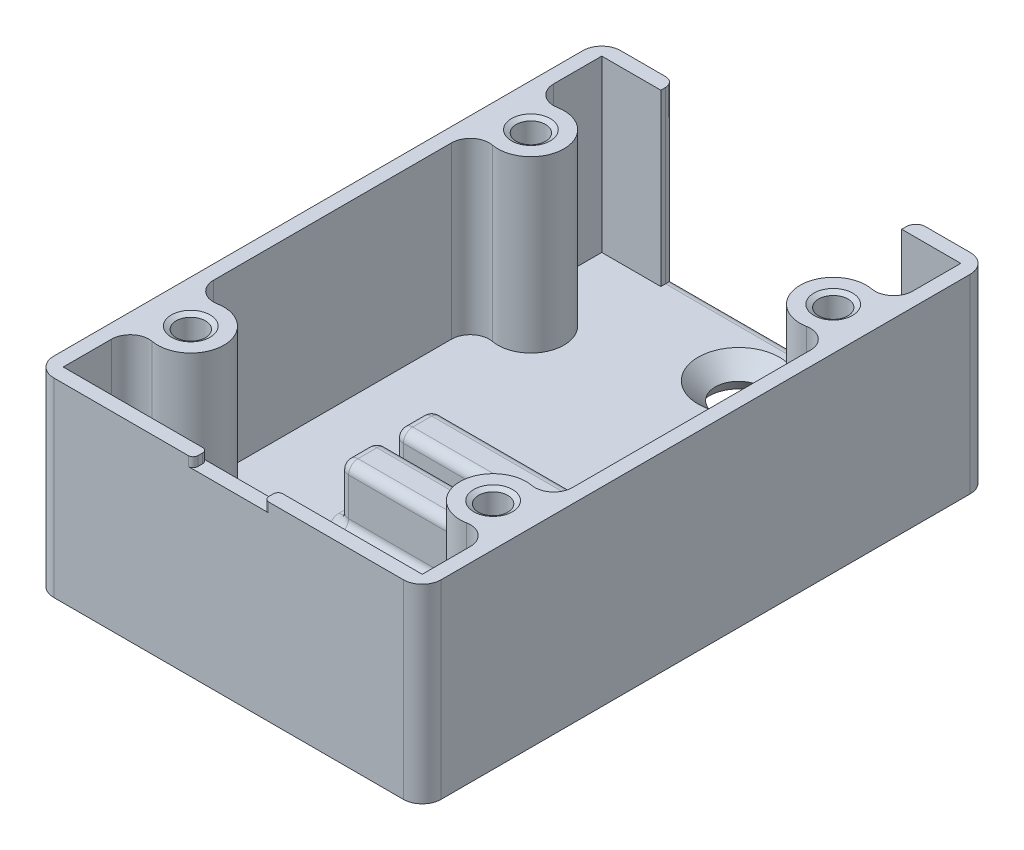
SolidWorks part; units mm, degrees
ref_plane "Спереди" through (0, 0, 0) normal (0, 0, 1) x (1, 0, 0)
ref_plane "Сверху" through (0, 0, 0) normal (0, 1, 0) x (1, 0, 0)
ref_plane "Справа" through (0, 0, 0) normal (1, 0, 0) x (0, 0, -1)
sketch "Эскиз1" plane through (0, 0, 0) normal (0, 1, 0) x (1, 0, 0)
  line L1 (-20.5, -30) -> (20.5, -30)
  line L2 (-20.5, -30) -> (-20.5, 30)
  line L3 (-20.5, 30) -> (20.5, 30)
  line L4 (20.5, -30) -> (20.5, 30)
  line L5 (0, 30) -> (0, -30) construction
  line L6 (-20.5, 0) -> (20.5, 0) construction
  circle A0 centre (0, 24) radius 2.3
  circle A1 centre (0, -24) radius 2.3
  point P0 (0, 0)
  dimension "D1" = 48
  dimension "D2" = 4.6
  dimension "D4" = 6
  dimension "D3" = 60
  dimension "D5" = 41
extrude "Бобышка-Вытянуть1" add sketch "Эскиз1" along normal blind 3
chamfer "Фаска1" distance 2 angle 45 2 edges at (0, 3, 26.3) (0, 3, -21.7)
sketch "Эскиз2" plane through (0, 3, 0) normal (0, 1, 0) x (1, 0, 0)
  line L0 (-20.5, 30) -> (20.5, 30)
  line L2 (-20.5, 30) -> (-20.5, -30)
  line L3 (-20.5, -30) -> (20.5, -30)
  line L4 (20.5, 30) -> (20.5, -30)
extrude "Вытянуть-Тонкостенный1" add sketch "Эскиз2" along normal blind 18 thin
sketch "Эскиз3" plane through (0, 21, 0) normal (0, 1, 0) x (1, 0, 0)
  line L0 (0, 32.0771) -> (0, 0) construction
  line L2 (-12.75, 27.9629) -> (12.75, 27.9629)
  line L3 (-12.75, 27.9629) -> (-12.75, 30.9933)
  line L4 (-12.75, 30.9933) -> (12.75, 30.9933)
  line L5 (12.75, 27.9629) -> (12.75, 30.9933)
  line L6 (0, 30.9933) -> (0, 27.9629) construction
  line L7 (-12.75, 29.4781) -> (12.75, 29.4781) construction
  point P3 (0, 29.4781)
  dimension "D1" = 25.5
extrude "Вырез-Вытянуть1" cut sketch "Эскиз3" against normal up to surface (18 mm away) up to face at (0, 3, 0)
sketch "Эскиз4" plane through (0, 3, 0) normal (0, 1, 0) x (1, 0, 0)
  line L0 (0, 32.478) -> (0, 0) construction
  line L1 (0, 0) -> (39.8357, 0) construction
  line L3 (20.5, -30) -> (20.5, 30) construction
  circle A0 centre (16, 18) radius 3.5
  circle A1 centre (-16, 18) radius 3.5
  circle A2 centre (16, -18) radius 3.5
  circle A3 centre (-16, -18) radius 3.5
  dimension "D1" = 7
  dimension "D3" = 4.5
  dimension "D2" = 18
extrude "Бобышка-Вытянуть2" add sketch "Эскиз4" along normal up to surface (18 mm away) up to face at (0, 21, -9.75)
sketch "Эскиз5" plane through (0, 21, 0) normal (0, 1, 0) x (1, 0, 0)
  line L0 (20.5, -30) -> (20.5, 30) construction
  circle A0 centre (16, 18) radius 1.55
  circle A1 centre (16, -18) radius 1.55
  circle A2 centre (-16, -18) radius 1.55
  circle A3 centre (-16, 18) radius 1.55
  dimension "D1" = 3.1
  dimension "D2" = 4.5
extrude "Вырез-Вытянуть2" cut sketch "Эскиз5" against normal blind 10
sketch "Эскиз6" plane through (0, 3, 0) normal (0, 1, 0) x (1, 0, 0)
  line L0 (-24.8451, -5.4) -> (34.7364, -5.4) construction
  line L1 (-8, -0.5) -> (8, -0.5)
  line L2 (-8, -0.5) -> (-8, -4.5)
  line L3 (-8, -4.5) -> (8, -4.5)
  line L4 (8, -0.5) -> (8, -4.5)
  line L5 (-8, -6.3) -> (8, -6.3)
  line L6 (8, -10.3) -> (8, -6.3)
  line L7 (0, 0) -> (0, 12.6053) construction
  line L8 (19, 28.5) -> (12.75, 28.5) construction
  line L9 (-8, -10.3) -> (8, -10.3)
  line L10 (-8, -10.3) -> (-8, -6.3)
  point P6 (0, -0.5)
  dimension "D1" = 4
  dimension "D2" = 33
  dimension "D3" = 16
  dimension "D4" = 1.8
extrude "Бобышка-Вытянуть3" add sketch "Эскиз6" along normal blind 6
sketch "Эскиз7" plane through (0, 21, 0) normal (0, 1, 0) x (1, 0, 0)
  line L1 (-3.75, -30.9828) -> (3.75, -30.9828)
  line L2 (-3.75, -30.9828) -> (-3.75, -26.3156)
  line L3 (-3.75, -26.3156) -> (3.75, -26.3156)
  line L4 (3.75, -30.9828) -> (3.75, -26.3156)
  line L5 (0, -26.3156) -> (0, -30.9828) construction
  line L6 (-3.75, -28.6492) -> (3.75, -28.6492) construction
  point P0 (0, -28.6492)
  dimension "D1" = 7.5
extrude "Вырез-Вытянуть3" cut sketch "Эскиз7" against normal blind 1
fillet "Скругление2" radius 0.5 4 edges at (-3.75, 20.5, 28.5) (-3.75, 20.5, 30) (3.75, 20.5, 30) (3.75, 20.5, 28.5)
fillet "Скругление3" radius 2 4 edges at (20.5, 10.5, -30) (-20.5, 10.5, -30) (-20.5, 10.5, 30) (20.5, 10.5, 30)
chamfer "Фаска4" distance 1.5 angle 30 10 edges at (0, 0, 26.3) (0, 0, -30) (-20.5, 0, 0) (0, 0, 30) (20.5, 0, 0) (0, 0, -21.7) (-19.9142, 0, -29.4142) (-19.9142, 0, 29.4142) (19.9142, 0, 29.4142) (19.9142, 0, -29.4142)
fillet "Скругление4" radius 1 24 edges at (0, 3, 0.5) (0, 3, 4.5) (8, 3, 2.5) (8, 6, 4.5) (8, 6, 0.5) (-8, 3, 2.5) (-8, 6, 0.5) (-8, 6, 4.5) (8, 9, 2.5) (-8, 9, 2.5) (-8, 9, 8.3) (-8, 3, 8.3) (8, 9, 8.3) (8, 3, 8.3) (8, 6, 6.3) (0, 9, 6.3) (-8, 6, 6.3) (0, 3, 6.3) (-8, 6, 10.3) (0, 9, 10.3) (8, 6, 10.3) (0, 3, 10.3) (0, 9, 0.5) (0, 9, 4.5)
chamfer "Фаска6" distance 0.5 angle 30 4 edges at (-16, 21, -16.45) (-16, 21, 19.55) (16, 21, 19.55) (16, 21, -16.45)
fillet "Скругление5" radius 1 3 edges at (12.75, 12, -30) (-12.75, 12, -30) (0, 3, -30)
fillet "Скругление7" radius 2 8 edges at (-19, 12, -16.1972) (-19, 12, -19.8028) (19, 12, 16.1972) (19, 12, 19.8028) (-19, 12, 19.8028) (-19, 12, 16.1972) (19, 12, -19.8028) (19, 12, -16.1972)
